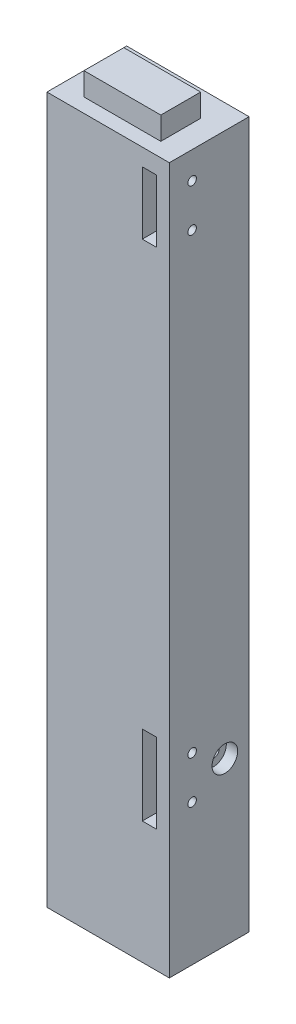
SolidWorks part; units mm, degrees
ref_plane "Front Plane" through (0, 0, 0) normal (0, 0, 1) x (1, 0, 0)
ref_plane "Top Plane" through (0, 0, 0) normal (0, 1, 0) x (1, 0, 0)
ref_plane "Right Plane" through (0, 0, 0) normal (1, 0, 0) x (0, 0, -1)
sketch "Sketch2" plane through (0, 0, 0) normal (0, 0, 1) x (1, 0, 0)
  line L1 (68.2625, 393.7) -> (-68.2625, 393.7)
  line L2 (68.2625, 393.7) -> (68.2625, -393.7)
  line L3 (68.2625, -393.7) -> (-68.2625, -393.7)
  line L4 (-68.2625, 393.7) -> (-68.2625, -393.7)
  line L5 (68.2625, 393.7) -> (-68.2625, -393.7) construction
  line L6 (68.2625, -393.7) -> (-68.2625, 393.7) construction
  point P0 (0, 0)
  dimension "D1" = 787.4
  dimension "D2" = 136.525
extrude "Boss-Extrude1" add sketch "Sketch2" along normal blind 88.9
sketch "Sketch4" plane through (0, 393.7, 0) normal (0, 1, 0) x (1, 0, 0)
  line L0 (68.2625, 0) -> (-68.2625, 0) construction
  line L1 (42.8625, -73.025) -> (-42.8625, -73.025)
  line L2 (42.8625, -73.025) -> (42.8625, -28.575)
  line L3 (42.8625, -28.575) -> (-42.8625, -28.575)
  line L4 (-42.8625, -73.025) -> (-42.8625, -28.575)
  line L5 (42.8625, -73.025) -> (-42.8625, -28.575) construction
  line L6 (42.8625, -28.575) -> (-42.8625, -73.025) construction
  line L7 (-68.2625, -88.9) -> (-68.2625, 0) construction
  point P0 (0, -50.8)
  dimension "D1" = 85.725
  dimension "D2" = 44.45
  dimension "D3" = 28.575
  dimension "D4" = 25.4
extrude "Boss-Extrude2" add sketch "Sketch4" along normal blind 25.4
sketch "Sketch5" plane through (-68.2625, 0, 0) normal (-1, 0, 0) x (0, 0, 1)
  line L0 (88.9, -393.7) -> (0, -393.7) construction
  line L1 (39.6875, -171.45) -> (14.2875, -171.45)
  line L2 (39.6875, -171.45) -> (39.6875, -254)
  line L3 (39.6875, -254) -> (14.2875, -254)
  line L4 (14.2875, -171.45) -> (14.2875, -254)
  line L5 (39.6875, -171.45) -> (14.2875, -254) construction
  line L6 (39.6875, -254) -> (14.2875, -171.45) construction
  line L7 (0, 393.7) -> (0, -393.7) construction
  point P0 (26.9875, -212.725)
  dimension "D1" = 82.55
  dimension "D2" = 139.7
  dimension "D3" = 25.4
  dimension "D4" = 14.2875
extrude "Cut-Extrude1" cut sketch "Sketch5" against normal blind 50.8
sketch "Sketch6" plane through (0, 0, 88.9) normal (0, 0, 1) x (1, 0, 0)
  line L0 (68.2625, -393.7) -> (68.2625, 393.7) construction
  line L1 (53.975, 374.65) -> (38.1, 374.65)
  line L2 (53.975, 374.65) -> (53.975, 304.8)
  line L3 (53.975, 304.8) -> (38.1, 304.8)
  line L4 (38.1, 374.65) -> (38.1, 304.8)
  line L5 (53.975, 374.65) -> (38.1, 304.8) construction
  line L6 (53.975, 304.8) -> (38.1, 374.65) construction
  line L7 (53.975, -168.275) -> (38.1, -168.275)
  line L8 (53.975, -168.275) -> (53.975, -257.175)
  line L9 (53.975, -257.175) -> (38.1, -257.175)
  line L10 (38.1, -168.275) -> (38.1, -257.175)
  line L11 (53.975, -168.275) -> (38.1, -257.175) construction
  line L12 (53.975, -257.175) -> (38.1, -168.275) construction
  line L13 (-68.2625, -393.7) -> (68.2625, -393.7) construction
  line L14 (68.2625, 393.7) -> (-68.2625, 393.7) construction
  point P0 (46.0375, 339.725)
  point P5 (46.0375, -212.725)
  dimension "D1" = 88.9
  dimension "D2" = 15.875
  dimension "D3" = 14.2875
  dimension "D4" = 136.525
  dimension "D5" = 15.875
  dimension "D6" = 69.85
  dimension "D7" = 19.05
extrude "Cut-Extrude2" cut sketch "Sketch6" against normal blind 50.8 contours L8 L9 L10 L7 | L2 L3 L4 L1
sketch "Sketch7" plane through (68.2625, 0, 0) normal (1, 0, 0) x (0, 0, -1)
  line L0 (-14.2875, -171.45) -> (-14.2875, -254) construction
  line L1 (-14.2875, -254) -> (-39.6875, -254) construction
  line L2 (-39.6875, -254) -> (-39.6875, -171.45) construction
  line L3 (-39.6875, -171.45) -> (-14.2875, -171.45) construction
  line L4 (-88.9, 304.8) -> (-88.9, 374.65) construction
  line L5 (-88.9, 374.65) -> (-38.1, 374.65) construction
  line L6 (-38.1, 374.65) -> (-38.1, 304.8) construction
  line L7 (-38.1, 304.8) -> (-88.9, 304.8) construction
  line L8 (-88.9, -257.175) -> (-88.9, -168.275) construction
  line L9 (-88.9, -168.275) -> (-38.1, -168.275) construction
  line L10 (-38.1, -168.275) -> (-38.1, -257.175) construction
  line L11 (-38.1, -257.175) -> (-88.9, -257.175) construction
  line L12 (-14.2875, -171.45) -> (-14.2875, -254)
  line L13 (-14.2875, -254) -> (-39.6875, -254)
  line L14 (-39.6875, -254) -> (-39.6875, -171.45)
  line L15 (-39.6875, -171.45) -> (-14.2875, -171.45)
  line L16 (-88.9, 304.8) -> (-88.9, 374.65)
  line L17 (-88.9, 374.65) -> (-38.1, 374.65)
  line L18 (-38.1, 374.65) -> (-38.1, 304.8)
  line L19 (-38.1, 304.8) -> (-88.9, 304.8)
  line L20 (-88.9, -257.175) -> (-88.9, -168.275)
  line L21 (-88.9, -168.275) -> (-38.1, -168.275)
  line L22 (-38.1, -168.275) -> (-38.1, -257.175)
  line L23 (-38.1, -257.175) -> (-88.9, -257.175)
  line L24 (-88.9, 374.65) -> (-38.1, 304.8) construction
  line L25 (-38.1, -168.275) -> (-88.9, -257.175) construction
  line L26 (-39.6875, -254) -> (-14.2875, -171.45) construction
  line L27 (-63.5, -168.275) -> (-63.5, -257.175) construction
  line L28 (-63.5, 374.65) -> (-63.5, 304.8) construction
  circle A0 centre (-26.9875, -212.725) radius 14.2875
  circle A1 centre (-26.9875, -212.725) radius 6.35
  circle A2 centre (-63.5, -188.9125) radius 4.7625
  circle A3 centre (-63.5, -236.5375) radius 4.7625
  circle A4 centre (-63.5, 315.9125) radius 4.7625
  circle A5 centre (-63.5, 363.5375) radius 4.7625
  point P21 (-63.5, -212.725)
  point P28 (-63.5, 339.725)
  dimension "D1" = 12.7
  dimension "D2" = 28.575
  dimension "D3" = 9.525
  dimension "D5" = 23.8125
  dimension "D8" = 9.525
  dimension "D10" = 23.8125
  dimension "D4" = 23.8125
  dimension "D6" = 25.4
  dimension "D7" = 25.4
  dimension "D9" = 23.8125
extrude "Cut-Extrude3" cut sketch "Sketch7" against normal blind 44.45 contours A3 | A2 | A4 | A5
extrude "Cut-Extrude4" cut sketch "Sketch7<3>" against normal blind 12.7 contours A0
sketch "Sketch7<3>" plane through (68.2625, 0, 0) normal (1, 0, 0) x (0, 0, -1) same geometry as "Sketch7"
extrude "Cut-Extrude5" cut sketch "Sketch7<4>" against normal through all contours A1 region at (68.2625, -212.725, 26.9875)
sketch "Sketch7<4>" plane through (68.2625, 0, 0) normal (1, 0, 0) x (0, 0, -1) same geometry as "Sketch7"
